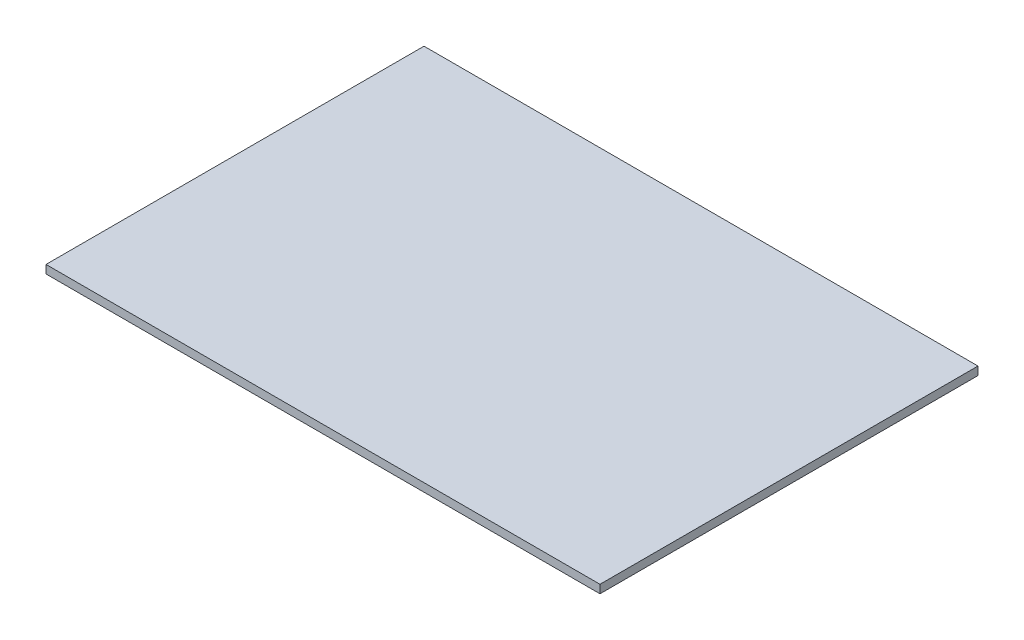
SolidWorks part; units mm, degrees
ref_plane "Front Plane" through (0, 0, 0) normal (0, 0, 1) x (1, 0, 0)
ref_plane "Top Plane" through (0, 0, 0) normal (0, 1, 0) x (1, 0, 0)
ref_plane "Right Plane" through (0, 0, 0) normal (1, 0, 0) x (0, 0, -1)
sketch "Sketch1" plane through (0, 0, 0) normal (0, 1, 0) x (1, 0, 0)
  line L0 (-425, 290) -> (425, 290)
  line L1 (-430, -295) -> (430, -295) construction
  line L2 (-430, -295) -> (-430, 295) construction
  line L3 (-430, 295) -> (430, 295) construction
  line L4 (430, -295) -> (430, 295) construction
  line L5 (-430, -295) -> (430, 295) construction
  line L6 (-430, 295) -> (430, -295) construction
  line L7 (425, -290) -> (425, 290)
  line L8 (-425, -290) -> (425, -290)
  line L9 (-425, -290) -> (-425, 290)
  point P0 (0, 0)
  dimension "D1" = 860
  dimension "D2" = 590
  dimension "D3" = 5
extrude "Boss-Extrude1" add sketch "Sketch1" along normal blind 12.7
equation "\"Crossbar_Width\"= 80mm"
equation "\"Vertical_Offset\"= \"Crossbar_Width\" / 2"
equation "\"Toolhead_Width\"= 100mm"
equation "\"Mechanical_Buffer\"= 30mm"
equation "\"Z_Interstitial\"= 100mm"
equation "\"Z_Interstitial_Sketch\"= \"Z_Interstitial\" + 1in"
